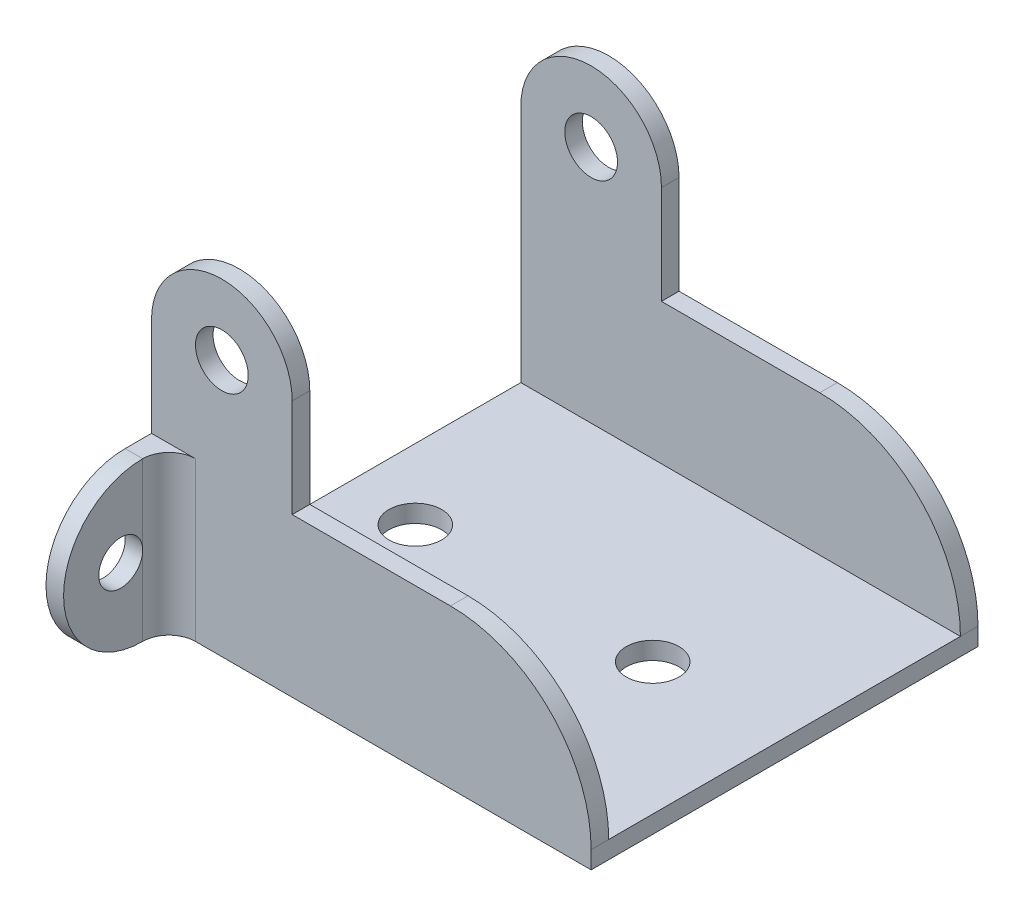
SolidWorks part; units mm, degrees
ref_plane "Alzado" through (0, 0, 0) normal (0, 0, 1) x (1, 0, 0)
ref_plane "Planta" through (0, 0, 0) normal (0, 1, 0) x (1, 0, 0)
ref_plane "Vista lateral" through (0, 0, 0) normal (1, 0, 0) x (0, 0, -1)
sketch "Croquis1" plane through (0, 0, 0) normal (0, 1, 0) x (1, 0, 0)
  line L1 (-12.5, 11) -> (12.5, 11)
  line L2 (-12.5, 11) -> (-12.5, -11)
  line L3 (-12.5, -11) -> (12.5, -11)
  line L4 (12.5, 11) -> (12.5, -11)
  line L5 (-12.5, 11) -> (12.5, -11) construction
  line L6 (-12.5, -11) -> (12.5, 11) construction
  point P0 (0, 0)
  dimension "D1" = 22
  dimension "D2" = 25
extrude "Saliente-Extruir1" add sketch "Croquis1" along normal blind 1
sketch "Croquis2" plane through (0, 1, 0) normal (0, 1, 0) x (1, 0, 0)
  line L0 (12.5, 0) -> (-12.5, 0) construction
  line L1 (12.5, -11) -> (12.5, 11) construction
  line L2 (-12.5, 11) -> (-12.5, -11) construction
  line L3 (-4.5, 11) -> (-4.5, 10)
  line L4 (-12.5, -11) -> (-4.5, -11)
  line L5 (-12.5, -11) -> (-12.5, -10)
  line L6 (-12.5, -10) -> (-4.5, -10)
  line L7 (-4.5, -11) -> (-4.5, -10)
  line L8 (-4.5, -11) -> (12.5, -11)
  line L9 (-4.5, -11) -> (-4.5, -10)
  line L10 (-4.5, -10) -> (12.5, -10)
  line L11 (12.5, -11) -> (12.5, -10)
  line L12 (-12.5, 10) -> (-4.5, 10)
  line L13 (-12.5, 11) -> (-12.5, 10)
  line L14 (-12.5, 11) -> (-4.5, 11)
  line L15 (12.5, 11) -> (12.5, 10)
  line L16 (-4.5, 10) -> (12.5, 10)
  line L17 (-4.5, 11) -> (12.5, 11)
  line M1 (12.5, -11) -> (12.5, 11)
  line M2 (12.5, 11) -> (-12.5, 11)
  line M3 (-12.5, 11) -> (-12.5, -11)
  line M4 (-12.5, -11) -> (12.5, -11)
  dimension "D1" = 8
  dimension "D2" = 1
extrude "Saliente-Extruir2" add sketch "Croquis2" along normal blind 17.6 contours L7 L6 M4 M3 | L12 L3 M3 M2 region at (-8.5, 1, -10.5) region at (-8.5, 1, 10.5)
extrude "Saliente-Extruir3" add sketch "Croquis2<3>" along normal blind 8 contours L10 L7 M4 M1 | L3 L16 M1 M2 region at (4, 1, -10.5) region at (4, 1, 10.5)
sketch "Croquis2<3>" plane through (0, 1, 0) normal (0, 1, 0) x (1, 0, 0) same geometry as "Croquis2"
fillet "Redondeo2" 2 edges at (-4.5, 18.6, 10.5) (-12.5, 18.6, 10.5) type full round first side face at (-4.5, 15, 10.5) second side face at (-12.5, 10.65, -1.25) middle face at (-8.5, 18.6, 10.5)
fillet "Redondeo3" radius 8 2 edges at (12.5, 9, 10.5) (12.5, 9, -10.5)
fillet "Redondeo4" 2 edges at (-4.5, 18.6, -10.5) (-12.5, 18.6, -10.5) type full round first side face at (-4.5, 13.8, -10.5) second side face at (-12.5, 9.4, -1.25) middle face at (-8.5, 18.6, -10.5)
sketch "Croquis4" plane through (0, 0, 11) normal (0, 0, 1) x (1, 0, 0)
  circle A0 centre (-8.5, 14.6) radius 1.5
  arc A1 (-4.5, 14.6) -> (-12.5, 14.6) centre (-8.5, 14.6) ccw construction
  dimension "D1" = 3
extrude "Cortar-Extruir1" cut sketch "Croquis4" against normal through all
sketch "Croquis5" plane through (0, 1, 0) normal (0, 1, 0) x (1, 0, 0)
  line L0 (-2.5, 10) -> (-2.5, -10) construction
  line L1 (-12.5, 10) -> (12.5, 10) construction
  line L2 (-12.5, -10) -> (12.5, -10) construction
  line L3 (12.5, -10) -> (12.5, 10) construction
  line L4 (-2.5, 10) -> (12.5, -10) construction
  line L5 (-2.5, -10) -> (12.5, 10) construction
  line L6 (-12.5, -10) -> (-4.5, 10) construction
  line L7 (-4.5, 10) -> (-4.5, -10) construction
  line L8 (-4.5, -10) -> (-12.5, 10) construction
  circle A0 centre (5, 0) radius 1.5
  circle A1 centre (-8.5, 0) radius 1.5
  dimension "D2" = 3
  dimension "D1" = 15
extrude "Cortar-Extruir2" cut sketch "Croquis5" against normal through all
sketch "Croquis6" plane through (0, 0, 11) normal (0, 0, 1) x (1, 0, 0)
  line L0 (-4.5, 9) -> (4.5, 9) construction
  line L1 (-12.5, 0) -> (-11.5, 0)
  line L2 (-12.5, 0) -> (-12.5, 9)
  line L3 (-12.5, 9) -> (-11.5, 9)
  line L4 (-11.5, 0) -> (-11.5, 9)
  dimension "D1" = 1
extrude "Saliente-Extruir4" add sketch "Croquis6" along normal blind 6
fillet "Redondeo5" 2 edges at (-12, 9, 17) (-12, 0, 17) type full round first side face at (-11.875, 9, 14.75) second side face at (-8.5, 0, 1.5) middle face at (-12, 4.5, 17)
fillet "Redondeo6" radius 1.5 1 edges
sketch "Croquis7" plane through (-12.5, 0, 0) normal (-1, 0, 0) x (0, 0, 1)
  line L0 (12.5, 4.5) -> (17, 4.5) construction
  line L1 (12.5, 4.5) -> (12.5, 9) construction
  arc A0 (12.5, 0) -> (12.5, 9) centre (12.5, 4.5) ccw construction
  circle A1 centre (13.75, 4.5) radius 1.25
  dimension "D1" = 2.5
extrude "Cortar-Extruir3" cut sketch "Croquis7" against normal up to next
sketch "Croquis8" plane through (0, 0, 0) normal (0, -1, 0) x (1, 0, 0)
  line L0 (12.5, 11) -> (12.5, -11) construction
  line L1 (12.5, 0) -> (-12.5, 0)
  line L2 (12.5, 0) -> (12.5, -11)
  line L3 (12.5, -11) -> (-12.5, -11)
  line L4 (-12.5, 0) -> (-12.5, -11)
extrude "Cortar-Extruir4" cut sketch "Croquis8" against normal through all
mirror "Simetría1" about plane through (0, 0, 0) normal (0, 0, 1) of bodies 108
sketch "Croquis9" plane through (-12.5, 0, 0) normal (-1, 0, 0) x (0, 0, 1)
  line L0 (-13.75, 3.25) -> (-13.75, 4.5)
  line L1 (-13.75, 4.5) -> (-15, 4.5)
  line L2 (13.75, 3.25) -> (13.75, 4.5)
  line L3 (13.75, 4.5) -> (15, 4.5)
  circle A0 centre (-13.75, 4.5) radius 1.25 construction
  circle A1 centre (13.75, 4.5) radius 1.25 construction
